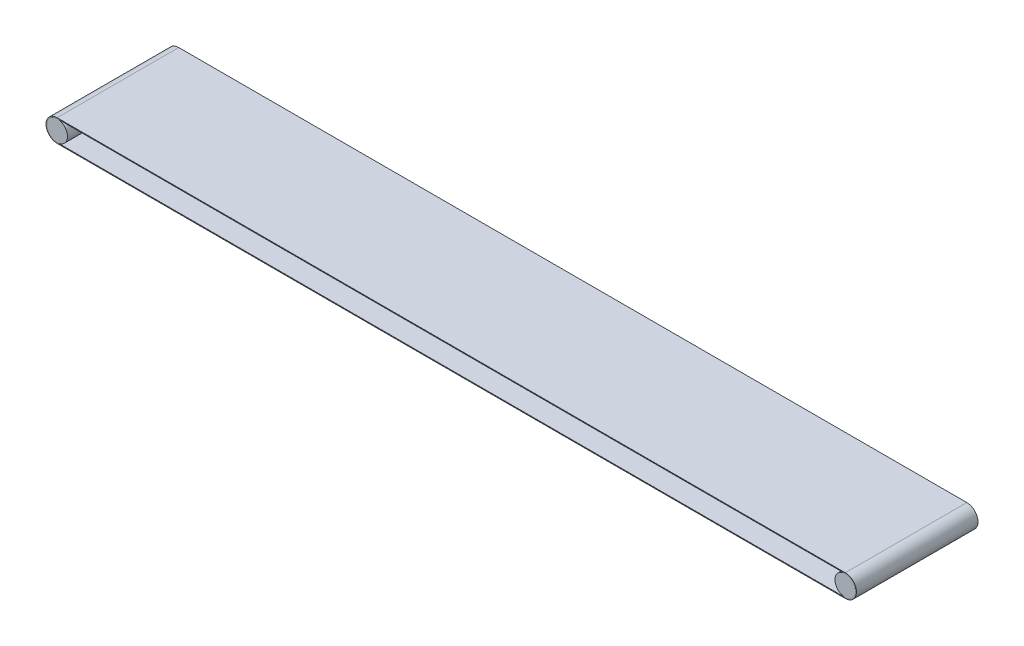
SolidWorks part; units mm, degrees
ref_plane "Front Plane" through (0, 0, 0) normal (0, 0, 1) x (1, 0, 0)
ref_plane "Top Plane" through (0, 0, 0) normal (0, 1, 0) x (1, 0, 0)
ref_plane "Right Plane" through (0, 0, 0) normal (1, 0, 0) x (0, 0, -1)
sketch "Sketch1" plane through (0, 0, 0) normal (0, 0, 1) x (1, 0, 0)
  line L0 (0, 0) -> (0, 327.5354) construction
  circle A0 centre (-972.5, 0) radius 25.5
  circle A1 centre (972.5, 0) radius 25.5
  dimension "D1" = 51
  dimension "D2" = 972.5
extrude "Boss-Extrude1" add sketch "Sketch1" along normal blind 300
sketch "Sketch2" plane through (0, 0, 300) normal (0, 0, 1) x (1, 0, 0)
  line L0 (-972.5, 25.5) -> (972.5, 25.5)
  line L1 (0, 0) -> (0, 99.0818) construction
  line L2 (-972.5, -25.5) -> (972.5, -25.5)
  line L3 (-972.5, 27.5) -> (972.5, 27.5)
  line L4 (-972.5, -27.5) -> (972.5, -27.5)
  line L5 (-972.5, 25.5) -> (-972.5, -25.5) construction
  circle A0 centre (-972.5, 0) radius 25.5 construction
  arc A1 (-972.5, 25.5) -> (-972.5, -25.5) centre (-972.5, 0) ccw
  arc A2 (972.5, 25.5) -> (972.5, -25.5) centre (972.5, 0) cw
  arc A3 (972.5, 27.5) -> (972.5, -27.5) centre (972.5, 0) cw
  arc A4 (-972.5, 27.5) -> (-972.5, -27.5) centre (-972.5, 0) ccw
  circle A5 centre (-972.5, 0) radius 25.5 construction
  point P10 (0, -25.5)
  point P12 (0, 25.5)
  dimension "D1" = 2
extrude "Boss-Extrude2" add sketch "Sketch2" against normal up to surface (300 mm away) separate body up to face at (947, 0, 0)
